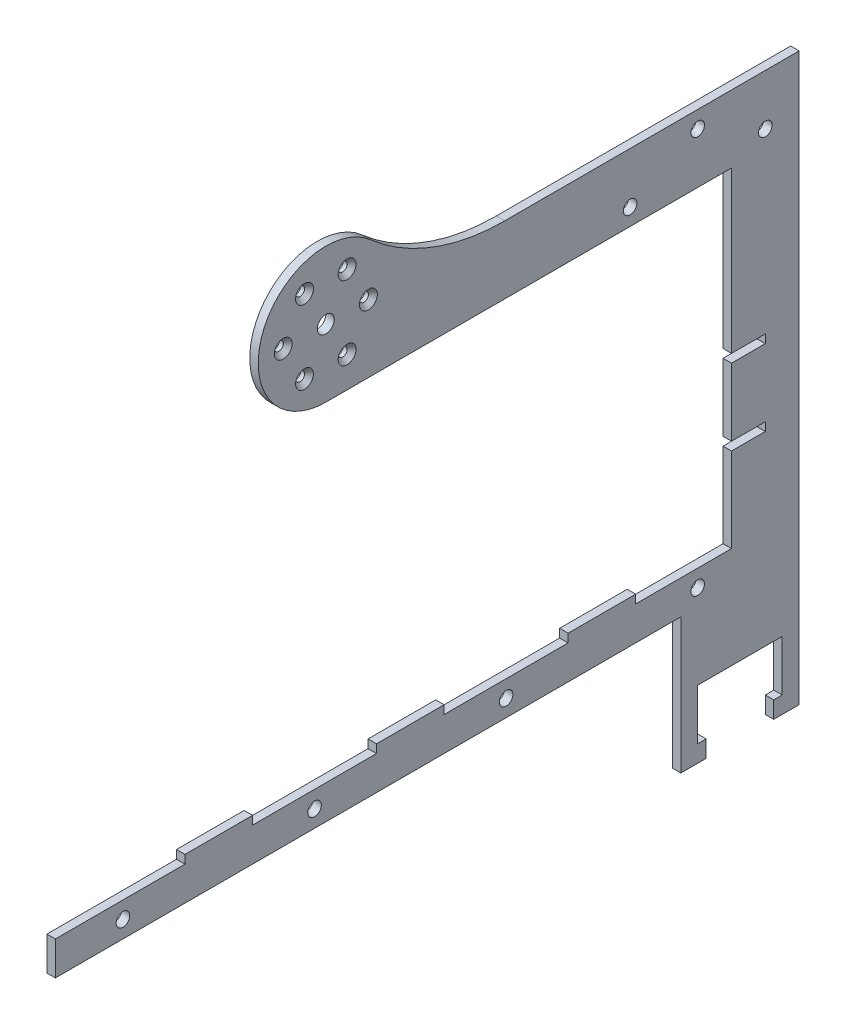
SolidWorks part; units mm, degrees
material "6061-T6 (SS)"
ref_plane "Front Plane" through (0, 0, 0) normal (0, 0, 1) x (1, 0, 0)
ref_plane "Top Plane" through (0, 0, 0) normal (0, 1, 0) x (1, 0, 0)
ref_plane "Right Plane" through (0, 0, 0) normal (1, 0, 0) x (0, 0, -1)
sketch "Sketch1" plane through (0, 0, 0) normal (1, 0, 0) x (0, 0, -1)
  line L0 (0, -80.9625) -> (0, 80.9625)
  line L3 (-177.8, 55.5625) -> (-25.4, 55.5625)
  line L6 (-25.4, 55.5625) -> (-25.4, -68.2625)
  line L7 (-25.4, -68.2625) -> (-279.4, -68.2625)
  line L8 (-279.4, -68.2625) -> (-279.4, -80.9625)
  line L10 (-279.4, -80.9625) -> (-44.45, -80.9625)
  line L11 (-44.45, -80.9625) -> (-44.45, -131.7625)
  line L12 (-44.45, -131.7625) -> (-34.925, -131.7625)
  line L16 (-9.525, -131.7625) -> (0, -131.7625)
  line L18 (0, -80.9625) -> (0, -131.7625)
  line L20 (-38.1, -106.3625) -> (-38.1, -125.4125)
  line L21 (-38.1, -125.4125) -> (-34.925, -125.4125)
  line L23 (-34.925, -131.7625) -> (-34.925, -125.4125)
  line L24 (-9.525, -131.7625) -> (-9.525, -125.4125)
  line L25 (-9.525, -125.4125) -> (-6.35, -125.4125)
  line L26 (-6.35, -125.4125) -> (-6.35, -106.3625)
  line L28 (-38.1, -106.3625) -> (-6.35, -106.3625)
  line L30 (0, 80.9625) -> (-110.5979, 80.9625)
  arc A0 (-160.9995, 100.0125) -> (-177.8, 55.5625) centre (-177.8, 80.9625) ccw
  arc A1 (-110.5979, 80.9625) -> (-160.9995, 100.0125) centre (-110.5979, 157.1625) cw
  point P4 (0, 0)
  dimension "D7" = 50.8
  dimension "D3" = 25.4
  dimension "D10" = 25.4
  dimension "D11" = 76.2
  dimension "D1" = 152.4
  dimension "D2" = 12.7
  dimension "D4" = 25.4
  dimension "D5" = 123.825
  dimension "D6" = 254
  dimension "D8" = 31.75
  dimension "D9" = 9.525
  dimension "D12" = 3.175
  dimension "D13" = 19.05
  dimension "D14" = 6.35
base flange "Base-Flange1" sketch "Sketch1" thickness 3.175 reverse thickness direction no parameters "D1"=3.175
sketch "Sketch8" plane through (0, 0, 0) normal (1, 0, 0) x (0, 0, -1)
  line L0 (-25.4, -7.9375) -> (-12.7, -7.9375)
  line L1 (-177.8, 55.5625) -> (-25.4, 55.5625) construction
  line L2 (-12.7, -7.9375) -> (-12.7, -4.7625)
  line L3 (-12.7, -4.7625) -> (-25.4, -4.7625)
  line L4 (-25.4, -4.7625) -> (-25.4, -7.9375)
  line L5 (-25.4, -4.7625) -> (-25.4, 55.5625) construction
  line L6 (-25.4, -68.2625) -> (-25.4, -36.5125) construction
  line L7 (-25.4, 55.5625) -> (-25.4, -68.2625) construction
  line L8 (-25.4, -33.3375) -> (-12.7, -33.3375)
  line L9 (-12.7, -33.3375) -> (-12.7, -36.5125)
  line L10 (-12.7, -36.5125) -> (-25.4, -36.5125)
  line L11 (-25.4, -36.5125) -> (-25.4, -33.3375)
  dimension "D1" = 25.4
  dimension "D2" = 63.5
  dimension "D5" = 12.7
  dimension "D6" = 3.175
extrude "Cut-Extrude2" cut sketch "Sketch8" against normal through all normal cut yes
sketch "Sketch11" plane through (0, 0, 0) normal (1, 0, 0) x (0, 0, -1)
  circle A0 centre (-177.8, 80.9625) radius 3.175
  arc A1 (-160.9995, 100.0125) -> (-177.8, 55.5625) centre (-177.8, 80.9625) ccw construction
  dimension "D1" = 6.35
extrude "Cut-Extrude4" cut sketch "Sketch11" against normal through all normal cut yes
sketch "Sketch21" plane through (0, 0, 0) normal (1, 0, 0) x (0, 0, -1)
  line L0 (-25.4, -68.2625) -> (-279.4, -68.2625) construction
  line L1 (-25.4, -36.5125) -> (-25.4, -68.2625) construction
  line L2 (-279.4, -68.2625) -> (-279.4, -80.9625) construction
  line L5 (0, -131.7625) -> (0, 80.9625) construction
  line L6 (0, 80.9625) -> (-110.5979, 80.9625) construction
  circle A0 centre (-38.1, -74.6125) radius 2.5527
  circle A1 centre (-110.0667, -74.6125) radius 2.5527
  circle A2 centre (-182.0333, -74.6125) radius 2.5527
  circle A3 centre (-254, -74.6125) radius 2.5527
  circle A8 centre (-12.7, 61.9125) radius 2.5527
  circle A9 centre (-38.1, 74.6125) radius 2.5527
  circle A10 centre (-63.5, 61.9125) radius 2.5527
  dimension "D1" = 6.35
  dimension "D2" = 5.1054
  dimension "D3" = 12.7
  dimension "D5" = 25.4
  dimension "D9" = 38.1
  dimension "D6" = 12.7
  dimension "D7" = 50.8
  dimension "D8" = 12.7
  dimension "D10" = 19.05
  dimension "D4" = 4
extrude "Cut-Extrude5" cut sketch "Sketch21" against normal through all normal cut yes
sketch "Sketch23" plane through (0, 0, 0) normal (1, 0, 0) x (0, 0, -1)
  line L0 (-25.4, -68.2625) -> (-279.4, -68.2625) construction
  line L1 (-230.7167, -68.2625) -> (-205.3167, -68.2625)
  line L2 (-230.7167, -68.2625) -> (-230.7167, -65.0875)
  line L3 (-230.7167, -65.0875) -> (-205.3167, -65.0875)
  line L4 (-205.3167, -68.2625) -> (-205.3167, -65.0875)
  line L5 (-254, -74.6125) -> (-230.7167, -65.0875) construction
  line L6 (-158.75, -68.2625) -> (-133.35, -68.2625)
  line L7 (-158.75, -68.2625) -> (-158.75, -65.0875)
  line L8 (-158.75, -65.0875) -> (-133.35, -65.0875)
  line L9 (-133.35, -68.2625) -> (-133.35, -65.0875)
  line L10 (-86.7833, -68.2625) -> (-61.3833, -68.2625)
  line L11 (-86.7833, -68.2625) -> (-86.7833, -65.0875)
  line L12 (-86.7833, -65.0875) -> (-61.3833, -65.0875)
  line L13 (-61.3833, -68.2625) -> (-61.3833, -65.0875)
  line L14 (-182.0333, -74.6125) -> (-205.3167, -65.0875) construction
  line L15 (-182.0333, -74.6125) -> (-158.75, -65.0875) construction
  line L16 (-110.0667, -74.6125) -> (-86.7833, -65.0875) construction
  dimension "D1" = 3.175
  dimension "D2" = 25.4
base flange "Tab1" sketch "Sketch23" thickness 3.175 reverse thickness direction no parameters "D1"=3.175
sketch "Sketch26" plane through (0, 0, 0) normal (1, 0, 0) x (0, 0, -1)
  circle A0 centre (-177.8, 80.9625) radius 16 construction
  point P0 (-161.8, 80.9625)
  point P12 (-169.8, 67.1061)
  point P13 (-185.8, 67.1061)
  point P14 (-193.8, 80.9625)
  point P15 (-185.8, 94.8189)
  point P16 (-169.8, 94.8189)
  dimension "D1" = 32
  dimension "D2" = 6
hole_wizard "CSK for M3 SFHCS1" positions "Sketch26" profile "Sketch25" countersink size "M3" standard "ANSI Metric" end condition up to next
sketch "Sketch25" plane through (0, 80.9625, 161.8) normal (0, 1, 0) x (0, 0, -1)
  line L0 (0, 0) -> (0, 3.175)
  line L1 (0, 3.175) -> (1.7, 3.175)
  line L2 (1.7, 3.175) -> (1.7, 1.66)
  line L3 (1.7, 1.66) -> (3.36, 0)
  line L5 (3.36, 0) -> (0, 0)
  line L6 (-1.7, 1.66) -> (-3.36, 0) construction
  line L11 (0, -6.35) -> (0, 107.95) construction
  dimension "Thru Hole Dia." = 3.4
  dimension "Thru Hole Depth" = 3.175
  dimension "Near C'Sink Dia." = 6.72
  dimension "Near C'Sink Angle" = 90
sketch "Bend-Lines1" [suppressed] plane through (0, 0, 0) normal (0, 1, 0) x (1, 0, 0)
sketch "Bounding-Box1" [suppressed] plane through (0, 0, 0) normal (0, 1, 0) x (1, 0, 0)
sheet metal parameters "Sheet-Metal1" thickness 3.175 parameters "D1"=3.175
flat pattern "Flat-Pattern1" [suppressed]
sketch "Bend-Lines2" plane through (0, 0, 0) normal (0, 1, 0) x (1, 0, 0)
sketch3d "Bounding-Box2" [suppressed]
  line L0 (-25.4, 25.4, 0) -> (330.2, 25.4, 0) construction
  line L1 (-25.4, -180.975, 0) -> (330.2, -180.975, 0) construction
  line L2 (-25.4, 25.4, 0) -> (-25.4, -180.975, 0) construction
  line L3 (330.2, 25.4, 0) -> (330.2, -180.975, 0) construction
sheet metal parameters "Sheet-Metal4" thickness 3.175 parameters "D1"=3.175
flat pattern "Flat-Pattern1"
sketch "Bend-Lines2" plane through (0, 0, 0) normal (0, 1, 0) x (1, 0, 0)
sketch3d "Bounding-Box2" [suppressed]
  line L0 (-25.4, 25.4, 0) -> (203.2, 25.4, 0) construction
  line L1 (-25.4, -180.975, 0) -> (203.2, -180.975, 0) construction
  line L2 (-25.4, 25.4, 0) -> (-25.4, -180.975, 0) construction
  line L3 (203.2, 25.4, 0) -> (203.2, -180.975, 0) construction
sheet metal parameters "Sheet-Metal6" thickness 3.175 parameters "D1"=3.175
flat pattern "Flat-Pattern1" [suppressed]
sketch "Bend-Lines2" plane through (0, 0, 0) normal (0, 1, 0) x (1, 0, 0)
sketch3d "Bounding-Box2" [suppressed]
  line L0 (-25.4, 25.4, 0) -> (203.2, 25.4, 0) construction
  line L1 (-25.4, -180.975, 0) -> (203.2, -180.975, 0) construction
  line L2 (-25.4, 25.4, 0) -> (-25.4, -180.975, 0) construction
  line L3 (203.2, 25.4, 0) -> (203.2, -180.975, 0) construction
sketch "Sketch14-1" [suppressed] plane through (-3.175, 0, 0) normal (-1, 0, 0) x (0, 0, 1)
  circle A0 centre (203.2, 77.7875) radius 16 construction
  circle A1 centre (203.2, 77.7875) radius 16 construction
  circle A2 centre (203.2, 77.7875) radius 16 construction
  circle A3 centre (203.2, 77.7875) radius 16 construction
  circle A4 centre (203.2, 77.7875) radius 16 construction
  circle A5 centre (203.2, 77.7875) radius 16 construction
  point P5 (203.2, 93.7875)
  dimension "D1" = 32
  dimension "D2" = 6
sheet metal parameters "Sheet-Metal12" thickness 3.175 parameters "D1"=3.175
flat pattern "Flat-Pattern12"
sketch "Bend-Lines3" plane through (0, 0, 0) normal (0, 1, 0) x (1, 0, 0)
sketch3d "Bounding-Box3" [suppressed]
  line L0 (177.8, -73.025, 0) -> (177.8, -104.775, 0) construction
  line L1 (152.4, -73.025, 0) -> (152.4, -104.775, 0) construction
  line L2 (177.8, -73.025, 0) -> (152.4, -73.025, 0) construction
  line L3 (177.8, -104.775, 0) -> (152.4, -104.775, 0) construction
sheet metal parameters "Sheet-Metal13" thickness 3.175 parameters "D1"=3.175
flat pattern "Flat-Pattern13"
sketch "Bend-Lines4" plane through (0, 0, 0) normal (0, 1, 0) x (1, 0, 0)
sketch3d "Bounding-Box4" [suppressed]
  line L0 (-50.8, -231.775, 0) -> (177.8, -231.775, 0) construction
  line L1 (-50.8, -107.95, 0) -> (177.8, -107.95, 0) construction
  line L2 (-50.8, -231.775, 0) -> (-50.8, -107.95, 0) construction
  line L3 (177.8, -231.775, 0) -> (177.8, -107.95, 0) construction
sheet metal parameters "Sheet-Metal14" thickness 3.175 parameters "D1"=3.175
flat pattern "Flat-Pattern14"
sketch "Bend-Lines5" plane through (0, 0, 0) normal (0, 1, 0) x (1, 0, 0)
sketch "Bounding-Box5" [suppressed] plane through (0, 0, 0) normal (0, 1, 0) x (1, 0, 0)
sheet metal parameters "Sheet-Metal15" thickness 3.175 parameters "D1"=3.175
flat pattern "Flat-Pattern1" [suppressed]
sketch "Bend-Lines2" plane through (0, 0, 0) normal (0, 1, 0) x (1, 0, 0)
sketch3d "Bounding-Box2" [suppressed]
  line L0 (109.6908, -298.3849, 0) -> (-172.9856, -257.5841, 0) construction
  line L1 (141.1244, -80.6061, 0) -> (-141.5519, -39.8053, 0) construction
  line L2 (109.6908, -298.3849, 0) -> (141.1244, -80.6061, 0) construction
  line L3 (-172.9856, -257.5841, 0) -> (-141.5519, -39.8053, 0) construction
sketch "Sketch14-1" plane through (-3.175, 0, 0) normal (-1, 0, 0) x (0, 0, 1)
  circle A0 centre (177.8, 82.55) radius 16 construction
  circle A1 centre (177.8, 82.55) radius 16 construction
  circle A2 centre (177.8, 82.55) radius 16 construction
  circle A3 centre (177.8, 82.55) radius 16 construction
  circle A4 centre (177.8, 82.55) radius 16 construction
  circle A5 centre (177.8, 82.55) radius 16 construction
  point P44 (193.8, 82.55)
  point P51 (185.8, 68.6936)
  point P52 (169.8, 68.6936)
  point P53 (161.8, 82.55)
  point P54 (169.8, 96.4064)
  point P55 (185.8, 96.4064)
  dimension "D1" = 32
  dimension "D2" = 6
  dimension "D3" = 6
sheet metal parameters "Sheet-Metal16" thickness 3.175 parameters "D1"=3.175
flat pattern "Flat-Pattern16"
sketch "Bend-Lines6" plane through (0, 0, 0) normal (0, 1, 0) x (1, 0, 0)
sketch3d "Bounding-Box6" [suppressed]
  line L0 (109.6908, -298.3849, 0) -> (-172.9856, -257.5841, 0) construction
  line L1 (141.1244, -80.6061, 0) -> (-141.5519, -39.8053, 0) construction
  line L2 (109.6908, -298.3849, 0) -> (141.1244, -80.6061, 0) construction
  line L3 (-172.9856, -257.5841, 0) -> (-141.5519, -39.8053, 0) construction
sheet metal parameters "Sheet-Metal17" thickness 3.175 parameters "D1"=3.175
flat pattern "Flat-Pattern16"
sketch "Bend-Lines6" plane through (0, 0, 0) normal (0, 1, 0) x (1, 0, 0)
sketch3d "Bounding-Box6" [suppressed]
  line L0 (109.6908, -295.2099, 0) -> (-172.9856, -254.4091, 0) construction
  line L1 (140.6755, -80.5413, 0) -> (-142.0008, -39.7405, 0) construction
  line L2 (109.6908, -295.2099, 0) -> (140.6755, -80.5413, 0) construction
  line L3 (-172.9856, -254.4091, 0) -> (-142.0008, -39.7405, 0) construction
